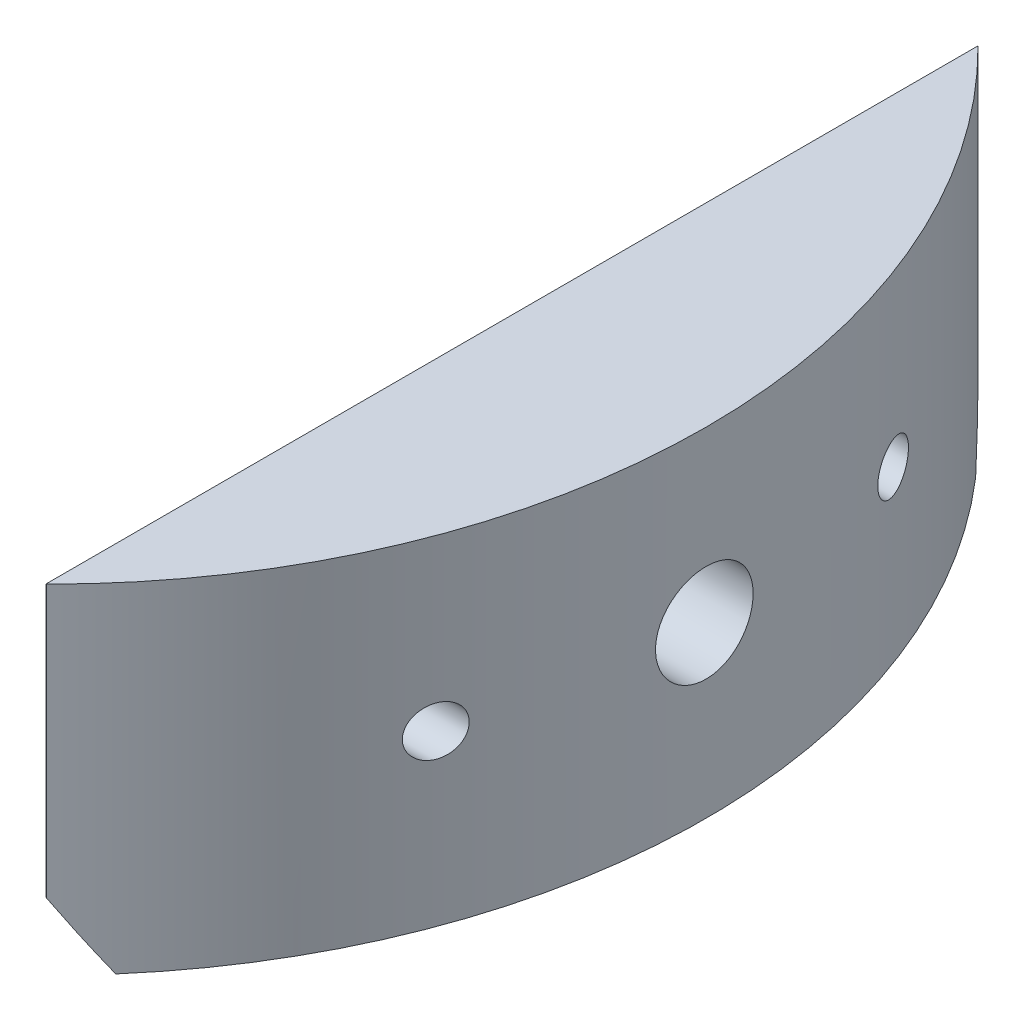
SolidWorks part; units mm, degrees
material "Plain Carbon Steel"
ref_plane "Front Plane" through (0, 0, 0) normal (0, 0, 1) x (1, 0, 0)
ref_plane "Top Plane" through (0, 0, 0) normal (0, 1, 0) x (1, 0, 0)
ref_plane "Right Plane" through (0, 0, 0) normal (1, 0, 0) x (0, 0, -1)
sketch "Sketch2" plane through (0, 0, 0) normal (0, 1, 0) x (1, 0, 0)
  line L0 (34.6715, 34.925) -> (34.6715, -34.925)
  line L2 (34.6715, 34.925) -> (34.6461, 34.925)
  line L3 (34.6715, 34.925) -> (34.6715, -34.925)
  line L4 (34.6715, -34.925) -> (34.6461, -34.925)
  line L5 (34.6461, 34.925) -> (34.6461, -34.925)
  line L13 (0, 0) -> (29.3279, 0) construction
  line L14 (0, 0) -> (47.5356, -12.7371) construction
  arc A0 (34.6715, -34.925) -> (34.6715, 34.925) centre (0, 0) ccw
  point P9 (34.6461, 0)
  dimension "D1" = 49.2125
  dimension "D2" = 69.85
  dimension "D3" = 0.0254
  dimension "D6" = 15
extrude "Boss-Extrude1" add sketch "Sketch2" along normal blind 25.4 contours L2 L5 L4 L0 | L0 A0 | L0 A0 region at (40.5685, 0, 0) region at (34.6588, 0, 0)
ref_plane "Plane1" through (49.2125, 0, 0) normal (1, 0, 0) x (0, 0, -1)
sketch "Sketch4" plane through (34.6461, 0, 0) normal (-1, 0, 0) x (0, 0, 1)
  line L0 (-34.925, 12.7) -> (34.925, 12.7) construction
  line L1 (-34.925, 25.4) -> (-34.925, 0) construction
  line L2 (0, 25.4) -> (0, 0) construction
  line L4 (-34.925, 0) -> (34.925, 0)
  line L10 (34.925, 0) -> (34.925, 25.4)
  line L11 (34.925, 25.4) -> (-34.925, 25.4)
  line L12 (-34.925, 25.4) -> (-34.925, 0)
  line L13 (-34.925, 0) -> (34.925, 0)
  line L14 (34.925, 0) -> (34.925, 25.4)
  line L15 (34.925, 25.4) -> (-34.925, 25.4)
  line L16 (-34.925, 25.4) -> (-34.925, 0)
  circle A0 centre (0, 12.7) radius 3.81
  circle A1 centre (0, 12.7) radius 1.27
  point P15 (0, 12.7)
  dimension "D1" = 7.62
  dimension "D2" = 2.54
  dimension "D3" = 0
extrude "Cut-Extrude2" cut sketch "Sketch4" against normal up to next contours A1
sketch "Sketch11" plane through (34.6461, 0, 0) normal (-1, 0, 0) x (0, 0, 1)
  circle A2 centre (0, 12.7) radius 3.6576
  dimension "D3" = 7.3152
extrude "Cut-Extrude4" cut sketch "Sketch11" along normal blind 7.62 from surface contours A2 starting at plane "Plane1"
sketch "Sketch13" plane through (49.2125, 0, 0) normal (1, 0, 0) x (0, 0, -1)
  line L1 (-6.2992, 12.7) -> (-7.6327, 12.7) construction
  line L2 (-6.2992, 12.7) -> (-4.9657, 12.7) construction
  line L4 (0, 12.7) -> (-34.925, 12.7) construction
  line L5 (-34.925, 25.4) -> (-34.925, 0) construction
  circle A0 centre (0, 12.7) radius 4.9657
  circle A1 centre (0, 12.7) radius 7.6327
  circle A2 centre (0, 12.7) radius 6.2992 construction
  dimension "D1" = 12.5984
  dimension "D2" = 2.667
wrap "Wrap3" [suppressed] sketch "Sketch13" source sketch "Sketch13" thickness 1.3208 parameters "D1"=1.3208
sketch "Sketch15" plane through (0, 0, 0) normal (1, 0, 0) x (0, 0, -1)
  line L0 (-34.925, 12.7) -> (34.925, 12.7) construction
  line L1 (0, 0) -> (0, 25.4) construction
  line L4 (-34.925, 0) -> (34.925, 0)
  line L5 (34.925, 0) -> (34.925, 25.4)
  line L6 (-34.925, 0) -> (34.925, 0)
  line L7 (-34.925, 25.4) -> (-34.925, 0)
  line L9 (34.925, 0) -> (34.925, 25.4)
  line L11 (-34.925, 25.4) -> (-34.925, 0)
  line L14 (34.925, 25.4) -> (-34.925, 25.4)
  line L15 (34.925, 25.4) -> (-34.925, 25.4)
  circle A0 centre (-17.145, 12.7) radius 1.8288
  circle A1 centre (17.145, 12.7) radius 1.8288
  dimension "D2" = 3.6576
  dimension "D3" = 17.145
extrude "Cut-Extrude5" cut sketch "Sketch15" along normal up to surface (46.7684 mm away) contours L0 A0 | A1 region at (0, 12.7, 17.145) region at (0, 12.7, -17.145) up to face at (49.0834, 13.5299, 3.5622)
chamfer "Chamfer1" distance 2.54 distance2 5.08 1 edges at (34.6461, 0, 0) first distance on face at (38.2941, 0, 0)
equation "\"Middle Coupler Inner Daimeter\"= 3.875in"
equation "\"Middle Coupler  Wall Thickness\" = 0.25in"
equation "\"Middle Coupler Bottom Thickness\"= 0.2in"
equation "\"Bearing Rail Offset\"= 0.45in"
equation "\"3-56 UNF Tap\"= 0.089in"
equation "\"3-48 Tap\"= 0.079in"
equation "\"3-56 UNF Clearance\"= 0.104in"
equation "\"3-48 Clearance\" = 0.104in"
equation "\"Ball Bearing Distance\"= 0.03in"
equation "\"TCA Outer Diameter\" = 6in"
equation "\"Interstage Aeroframe Wall Thickness\" = 0.072in"
equation "\"Compression Spring OD\"= 0.42in"
equation "\"10-24 Tap\"= 0.1495in"
equation "\"10-24 Clearance\"= 0.196in"
equation "\"Lower Stage Fuselage Wall Thickness\" = 0.25in"
equation "\"6-32 Tap\" = 0.107in"
equation "\"6-32 Clearance\" = 0.144in"
equation "\"1/4-20 Tap\" = 0.201in"
equation "\"12-24 Tap\" = 0.177in"
equation "\"D1@Sketch2\"=\"Middle Coupler Inner Daimeter\"/2"
equation "\"D2@Sketch15\"=\"6-32 Clearance\""
